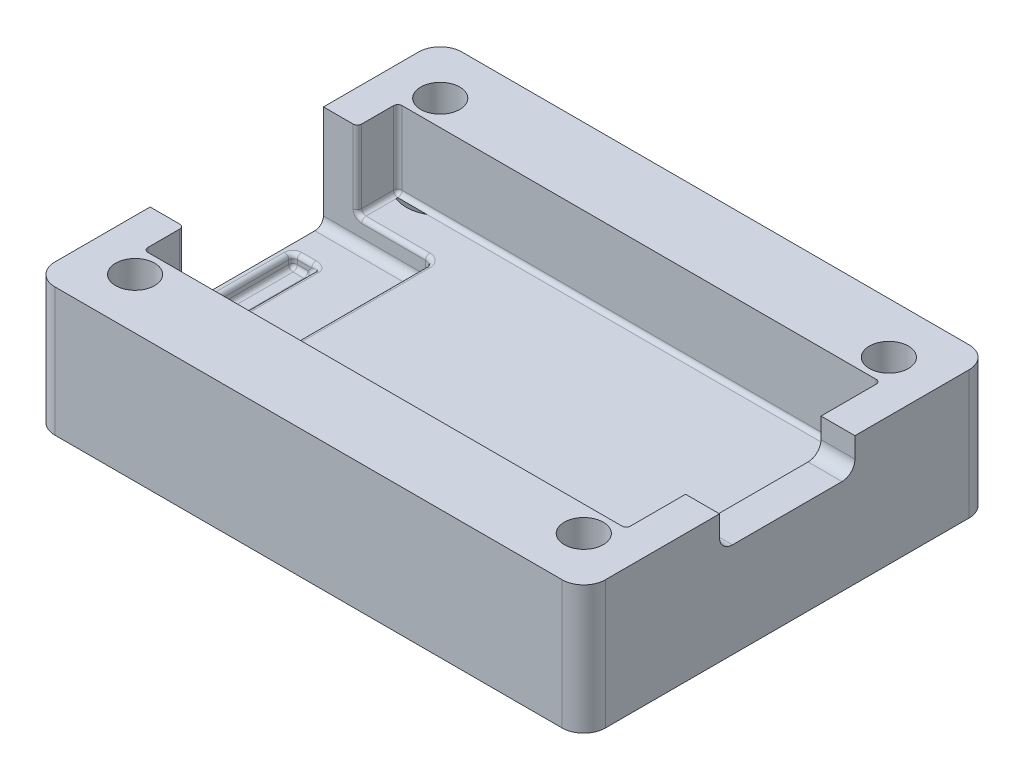
SolidWorks part; units mm, degrees
ref_plane "Front Plane" through (0, 0, 0) normal (0, 0, 1) x (1, 0, 0)
ref_plane "Top Plane" through (0, 0, 0) normal (0, 1, 0) x (1, 0, 0)
ref_plane "Right Plane" through (0, 0, 0) normal (1, 0, 0) x (0, 0, -1)
sketch "Sketch1" plane through (0, 0, 0) normal (0, 1, 0) x (1, 0, 0)
  line L0 (58.9293, 5.9568) -> (58.9293, -15.4892) construction
  line L1 (58.9293, 7.2268) -> (26.4813, 7.2268)
  line L2 (58.9293, 7.2268) -> (58.9293, -16.7592)
  line L3 (58.9293, -16.7592) -> (26.4813, -16.7592)
  line L4 (26.4813, 7.2268) -> (26.4813, -16.7592)
  line L5 (58.9293, 7.2268) -> (26.4813, -16.7592) construction
  line L6 (58.9293, -16.7592) -> (26.4813, 7.2268) construction
  line L7 (27.7513, 7.2268) -> (57.6593, 7.2268) construction
  line L8 (26.4813, -15.4892) -> (26.4813, 5.9568) construction
  line L9 (57.6593, -16.7592) -> (27.7513, -16.7592) construction
  point P0 (0, 0)
extrude "Boss-Extrude1" add sketch "Sketch1" along normal blind 7.572
sketch "Sketch3" plane through (0, 7.572, 0) normal (0, 1, 0) x (1, 0, 0)
  line L1 (56.9293, -12.2592) -> (28.4813, -12.2592)
  line L2 (56.9293, -12.2592) -> (56.9293, 2.7268)
  line L3 (56.9293, 2.7268) -> (28.4813, 2.7268)
  line L4 (28.4813, -12.2592) -> (28.4813, 2.7268)
  line L5 (56.9293, -12.2592) -> (28.4813, 2.7268) construction
  line L6 (56.9293, 2.7268) -> (28.4813, -12.2592) construction
  line L8 (56.9293, 2.4728) -> (56.9293, -0.7748) construction
  line L9 (28.7353, 2.7268) -> (56.6753, 2.7268) construction
  line L10 (56.6753, -12.2592) -> (28.7353, -12.2592) construction
  line L11 (28.4813, -12.0052) -> (28.4813, -9.8753) construction
  point P0 (0, 0)
extrude "Cut-Extrude1" cut sketch "Sketch3" against normal blind 4.572
fillet "Fillet1" radius 1.27 4 edges at (26.4813, 3.786, -7.2268) (58.9293, 3.786, -7.2268) (26.4813, 3.786, 16.7592) (58.9293, 3.786, 16.7592)
fillet "Fillet2" radius 0.254 4 edges at (56.9293, 5.286, -2.7268) (56.9293, 5.286, 12.2592) (28.4813, 5.286, 12.2592) (28.4813, 5.286, -2.7268)
fillet "Fillet3" radius 0.254 8 edges at (56.8549, 3, 12.1848) (42.7053, 3, 12.2592) (28.5557, 3, 12.1848) (28.4813, 3, 4.7662) (28.5557, 3, -2.6524) (42.7053, 3, -2.7268) (56.8549, 3, -2.6524) (56.9293, 3, 4.7662)
sketch "Sketch5" plane through (26.4813, 0, 0) normal (-1, 0, 0) x (0, 0, 1)
  line L0 (-5.9568, 7.572) -> (15.4892, 7.572) construction
  line L1 (9.8753, 7.572) -> (-0.3429, 7.572) construction
  line L2 (9.8753, 7.572) -> (9.8753, 1.5)
  line L3 (9.8753, 1.5) -> (-0.3429, 1.5)
  line L4 (-0.3429, 7.572) -> (-0.3429, 1.5)
  line L5 (-5.9568, 0) -> (15.4892, 0) construction
  line L11 (-0.3429, 7.572) -> (9.8753, 7.572)
  line L15 (-0.3429, 7.572) -> (9.8753, 7.572)
  line L16 (-0.3429, 8.072) -> (-0.3429, 7.572)
  line L17 (9.8753, 8.072) -> (-0.3429, 8.072)
  line L18 (9.8753, 7.572) -> (9.8753, 8.072)
  line L19 (-0.3429, 7.572) -> (9.8753, 7.572) construction
  line L20 (-0.3429, 8.072) -> (-0.3429, 7.572) construction
  line L21 (9.8753, 8.072) -> (-0.3429, 8.072) construction
  line L22 (9.8753, 7.572) -> (9.8753, 8.072) construction
  point P8 (4.7662, 7.572)
  point P9 (4.7662, 0)
  dimension "D1" = 1.5
  dimension "D2" = 0
extrude "Cut-Extrude3" cut sketch "Sketch5" against normal up to surface (6.5278 mm away)
fillet "Fillet4" radius 0.508 5 edges at (29.7452, 1.5, -0.3429) (29.7452, 1.5, 9.8753) (33.0092, 1.5, 4.7662) (33.0092, 2.25, 9.8753) (33.0092, 2.25, -0.3429)
ref_plane "Plane1" through (56.6753, 3, -2.4728) normal (0, 0, -1) x (-1, 0, 0)
sketch "Sketch7" plane through (58.9293, 0, 0) normal (1, 0, 0) x (0, 0, -1)
  line L0 (5.9568, 7.572) -> (-0.7748, 7.572) construction
  line L1 (-0.7748, 7.572) -> (-8.7576, 7.572)
  line L2 (-0.7748, 7.572) -> (-0.7748, 5.6091)
  line L3 (-0.7748, 5.6091) -> (-8.7576, 5.6091)
  line L4 (-8.7576, 7.572) -> (-8.7576, 5.6091)
  line L5 (-15.4892, 0) -> (5.9568, 0) construction
  line L6 (2.4728, 6.1091) -> (-12.0272, 6.1091) construction
  line L7 (2.4728, 6.1091) -> (-12.0272, 6.1091) construction
  point P6 (-4.7662, 5.6091)
  point P9 (-4.7662, 0)
  dimension "D1" = 0.5
extrude "Cut-Extrude4" cut sketch "Sketch7" against normal up to surface (2 mm away) up to face at (56.9293, 5.413, 4.7662)
fillet "Fillet5" radius 0.762 2 edges at (57.9293, 5.6091, 8.7576) (57.9293, 5.6091, 0.7748)
sketch "Sketch8" plane through (0, 0, 0) normal (0, -1, 0) x (-1, 0, 0)
  line L0 (-26.4813, 5.9568) -> (-26.4813, -15.4892) construction
  line L16 (-58.9293, -16.7592) -> (-26.4813, -16.7592) construction
  line L17 (-58.9293, -16.7592) -> (-58.9293, 7.2268) construction
  line L18 (-58.9293, 7.2268) -> (-26.4813, 7.2268) construction
  line L19 (-26.4813, -16.7592) -> (-26.4813, 7.2268) construction
  line L20 (-57.6593, 7.2268) -> (-27.7513, 7.2268) construction
  line L21 (-58.9293, -15.4892) -> (-58.9293, 5.9568) construction
  line L22 (-27.7513, -16.7592) -> (-57.6593, -16.7592) construction
  line L23 (-57.9293, 6.2268) -> (-27.4813, 6.2268) construction
  line L24 (-27.4813, -15.7592) -> (-27.4813, 6.2268) construction
  line L25 (-57.9293, -15.7592) -> (-27.4813, -15.7592) construction
  line L26 (-57.9293, -15.7592) -> (-57.9293, 6.2268) construction
  circle A0 centre (-55.9293, 4.2268) radius 2
  circle A1 centre (-29.4813, 4.2268) radius 2
  circle A2 centre (-29.4813, -13.7592) radius 2
  circle A3 centre (-55.9293, -13.7592) radius 2
  dimension "D1" = 4
  dimension "D2" = 1
extrude "Cut-Extrude5" cut sketch "Sketch8" against normal blind 3
sketch "Sketch9" plane through (0, 0, 0) normal (0, -1, 0) x (-1, 0, 0)
  circle A0 centre (-55.9293, 4.2268) radius 1.15
  circle A2 centre (-29.4813, 4.2268) radius 1.15
  circle A3 centre (-29.4813, -13.7592) radius 1.15
  circle A4 centre (-55.9293, -13.7592) radius 1.15
  circle A8 centre (-55.9293, -13.7592) radius 2 construction
  circle A9 centre (-55.9293, 4.2268) radius 2 construction
  circle A10 centre (-29.4813, 4.2268) radius 2 construction
  circle A11 centre (-29.4813, -13.7592) radius 2 construction
  dimension "D1" = 2.3
extrude "Cut-Extrude7" cut sketch "Sketch9" against normal through all
ref_plane "Plane2" through (0, 0, 7.4071) normal (0, 0, 1) x (1, 0, 0)
ref_plane "Plane3" through (0, 0, 1.9071) normal (0, 0, -1) x (-1, 0, 0)
sketch "Sketch10" plane through (0, 0, 7.4071) normal (0, 0, 1) x (1, 0, 0)
  line L0 (26.9369, 4.4275) -> (26.9369, 3.4275) construction
  line L1 (26.9369, 4.4275) -> (26.9369, 3.4275) construction
  line L2 (26.9369, 3.4275) -> (27.4369, 3.4275) construction
  line L3 (26.9369, 1.75) -> (28.8369, 1.75)
  line L4 (26.9369, 3.4275) -> (27.4369, 3.4275) construction
  line L5 (27.4369, 3.4275) -> (28.3369, 4.4275) construction
  line L6 (27.4369, 3.4275) -> (28.3369, 4.4275) construction
  line L7 (28.3369, 4.4275) -> (26.9369, 4.4275) construction
  line L12 (28.8369, 1.75) -> (27.9369, 0.75)
  line L13 (27.9369, 0.75) -> (26.9369, 0.75)
  line L14 (26.9369, 0.75) -> (26.9369, 1.75)
  line L15 (27.7513, 0) -> (57.6593, 0) construction
  line L16 (27.4369, 3.4275) -> (27.4369, 0.75) construction
  line L17 (27.7513, 0) -> (57.6593, 0) construction
  line L18 (28.3369, 4.4275) -> (28.3369, 1.75) construction
  dimension "D1" = 0.75
  dimension "D2" = 0.5
extrude "Cut-Extrude8" cut sketch "Sketch10" against normal up to surface (5.5 mm away) up to plane "Plane3"
fillet "Fillet8" radius 0.254 9 edges at (28.4813, 5.413, 9.8753) (28.5557, 3.0744, 9.8753) (30.6182, 3, 9.8753) (32.8604, 3, 9.7265) (33.0092, 3, 4.7662) (32.8604, 3, -0.1941) (28.4813, 5.413, -0.3429) (28.5557, 3.0744, -0.3429) (30.6182, 3, -0.3429)
fillet "Fillet10" radius 0.254 12 edges at (27.7744, 1.5, 1.9071) (27.7744, 1.5, 7.4071) (26.9369, 1.125, 1.9071) (26.9369, 1.125, 7.4071) (26.9369, 1.5, 4.6571) (28.2744, 1.125, 1.9071) (28.6119, 1.5, 4.6571) (28.2744, 1.125, 7.4071) (27.4369, 0.75, 1.9071) (27.9369, 0.75, 4.6571) (27.4369, 0.75, 7.4071) (26.9369, 0.75, 4.6571)
